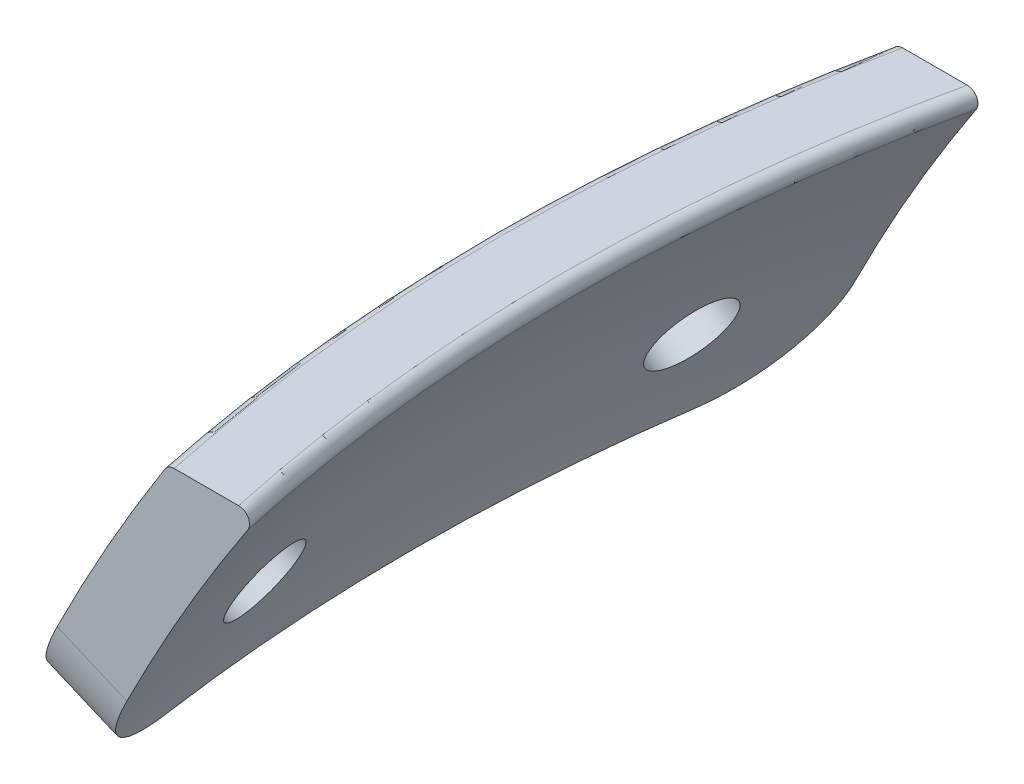
SolidWorks part; units mm, degrees
material "Polyether Polyol"
ref_plane "Front Plane" through (0, 0, 0) normal (0, 0, 1) x (1, 0, 0)
ref_plane "Top Plane" through (0, 0, 0) normal (0, 1, 0) x (1, 0, 0)
ref_plane "Right Plane" through (0, 0, 0) normal (1, 0, 0) x (0, 0, -1)
sketch "Sketch1" plane through (0, 0, 0) normal (0, 0, 1) x (1, 0, 0)
  line L2 (-166.6461, 194.6685) -> (-145.5262, 194.6685) construction
  line L3 (-180.7804, 167.7876) -> (-174.3518, 165.0174) construction
  line L6 (-166.6461, 194.6685) -> (-158.3162, 194.6685)
  line L7 (-180.7804, 167.7876) -> (-174.3518, 165.0174)
  line L8 (0, 0) -> (0, 244.1177) construction
  arc A0 (-166.6461, 194.6685) -> (-180.7804, 167.7876) centre (0, 89.8878) ccw construction
  arc A1 (-162.7328, 187.6685) -> (-174.3518, 165.0174) centre (0, 89.8878) ccw construction
  arc A2 (-166.6461, 194.6685) -> (-180.7804, 167.7876) centre (0, 89.8878) ccw
  arc A3 (-162.7328, 187.6685) -> (-174.3518, 165.0174) centre (0, 89.8878) ccw
  arc A4 (-162.7328, 187.6685) -> (-158.3162, 194.6685) centre (0, 89.8878) cw
revolve "Revolve1" add sketch "Sketch1" angle 25 mid plane about L8
sketch "Sketch2" plane through (0, 0, 0) normal (0, 0, 1) x (1, 0, 0)
  line L0 (0, 89.8878) -> (-169.1576, 176.0779) construction
  line L1 (0, 0) -> (0, 244.1177) construction
  arc A1 (-162.7328, 187.6685) -> (-174.3518, 165.0174) centre (0, 89.8878) ccw construction
  dimension "D1" = 63
ref_plane "Plane1" through (36.3604, 71.3612, 0) normal (0.454, 0.891, 0) x (-0.891, 0.454, 0)
sketch "Sketch4" plane through (36.3604, 71.3612, 0) normal (0.454, 0.891, 0) x (-0.891, 0.454, 0)
  line L0 (219.8801, 19.237) -> (239.1484, 20.9228) construction
  line L1 (219.5446, 23.0724) -> (238.8129, 24.7581)
  line L2 (219.5446, 23.0724) -> (219.8801, 19.237)
  line L3 (40.8082, 0) -> (230.6582, 0) construction
  line L4 (219.8801, 19.237) -> (239.1484, 20.9228)
  line L5 (238.8129, 24.7581) -> (239.1484, 20.9228)
  dimension "D1" = 7.7
  dimension "D2" = 5
revolve "Cut-Revolve1" cut sketch "Sketch4" angle 360 about L0
mirror "Mirror1" about plane through (0, 0, 0) normal (0, 0, 1) of "Cut-Revolve1"
sketch "Sketch5" plane through (0, 0, 0) normal (0, 1, 0) x (1, 0, 0)
  line L1 (-154.5635, 34.2659) -> (-201.5408, 34.2659)
  line L2 (-154.5635, 34.2659) -> (-154.5635, -34.2659)
  line L3 (-154.5635, -34.2659) -> (-201.5408, -34.2659)
  line L4 (-201.5408, 34.2659) -> (-201.5408, -34.2659)
extrude "Cut-Extrude2" cut sketch "Sketch5" along normal through all flip side to cut
fillet "Fillet1" radius 10 2 edges
fillet "Fillet2" radius 1 2 edges at (-166.6461, 194.6685, 0) (-158.3162, 194.6685, 0)
